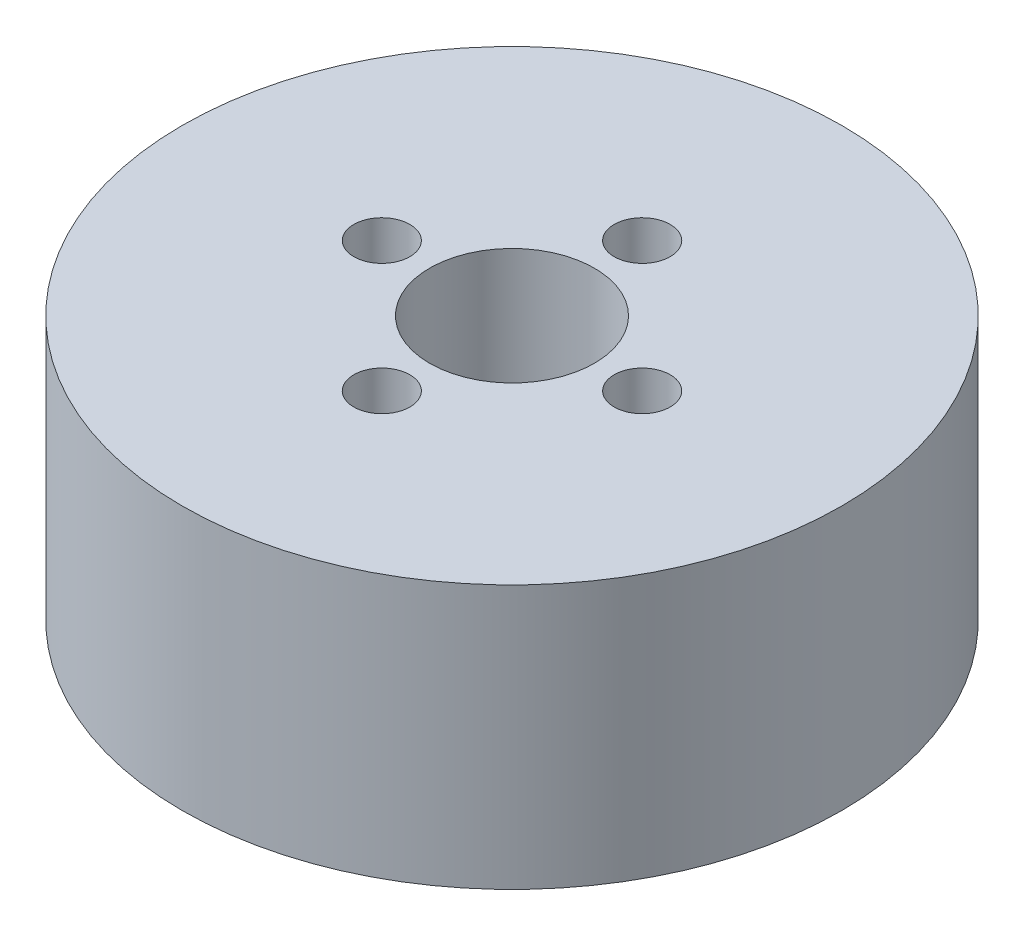
SolidWorks part; units mm, degrees
ref_plane "Front Plane" through (0, 0, 0) normal (0, 0, 1) x (1, 0, 0)
ref_plane "Top Plane" through (0, 0, 0) normal (0, 1, 0) x (1, 0, 0)
ref_plane "Right Plane" through (0, 0, 0) normal (1, 0, 0) x (0, 0, -1)
sketch "Sketch1" plane through (0, 0, 0) normal (0, 1, 0) x (1, 0, 0)
  circle A0 centre (0, 0) radius 20
  dimension "FLANGE_OD" = 40
extrude "Boss-Extrude1" add sketch "Sketch1" along normal blind 16
sketch "Sketch2" plane through (0, 0, 0) normal (0, 1, 0) x (1, 0, 0)
  circle A0 centre (0, 0) radius 5
  dimension "BORE_D" = 10
extrude "Cut-Extrude1" cut sketch "Sketch2" along normal through all
sketch "Sketch3" plane through (0, 16, 0) normal (0, 1, 0) x (1, 0, 0)
  circle A0 centre (0, 0) radius 7.8965 construction
  circle A1 centre (-7.8965, 0) radius 1.6982
  dimension "BOLT_D" = 3.3964
  dimension "BOLT_PCD" = 15.7931
extrude "Cut-Extrude2" cut sketch "Sketch3" against normal blind 12.4252
pattern_circular "CirPattern1" count 4 over 360 about axis through (0, 0, 0) along (0, 1, 0) of "Cut-Extrude2"
